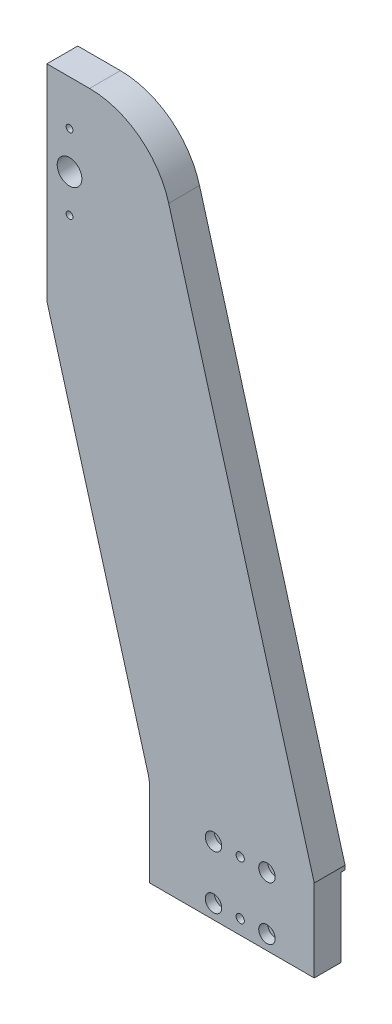
SolidWorks part; units mm, degrees
material "3.3547 (EN-AW 5083)"
ref_plane "Alzado" through (0, 0, 0) normal (0, 0, 1) x (1, 0, 0)
ref_plane "Planta" through (0, 0, 0) normal (0, 1, 0) x (1, 0, 0)
ref_plane "Vista lateral" through (0, 0, 0) normal (1, 0, 0) x (0, 0, -1)
sketch "Croquis1" plane through (0, 0, 0) normal (0, 0, 1) x (1, 0, 0)
  line L0 (80, 0) -> (80, 40)
  line L1 (-50, 320) -> (-29.2688, 320)
  line L2 (-50, 320) -> (-50, 220)
  line L3 (0, 0) -> (80, 0)
  line L4 (9.2285, 290.8607) -> (80, 40)
  line L9 (-50, 220) -> (-0.7513, 45.4303)
  line L11 (0, 40) -> (0, 0)
  arc A2 (9.2285, 290.8607) -> (-29.2688, 320) centre (-29.2688, 280) ccw
  arc A3 (0, 40) -> (-0.7513, 45.4303) centre (-20, 40) ccw
  point P14 (0, 42.7671)
  dimension "D7" = 20
  dimension "D9" = 40
  dimension "D1" = 40
  dimension "D2" = 320
  dimension "D3" = 80
  dimension "D4" = 50
  dimension "D5" = 100
  dimension "D6" = 40
extrude "Saliente-Extruir1" add sketch "Croquis1" along normal blind 15
sketch "Croquis2" plane through (0, 0, 0) normal (0, 0, -1) x (-1, 0, 0)
  line L0 (29.2688, 320) -> (50, 320) construction
  line L2 (50, 320) -> (50, 220) construction
  circle A0 centre (39, 280) radius 6
  dimension "D3" = 12
  dimension "D1" = 40
  dimension "D2" = 11
extrude "Cortar-Extruir1" cut sketch "Croquis2" against normal through all
hole_wizard "Perforador para roscar para macho de roscar para M44" positions "Croquis7" profile "Croquis8" hole size "M4" standard "DIN"
sketch "Croquis7" plane through (0, 0, 15) normal (0, 0, 1) x (1, 0, 0)
  line L0 (-39, 298.25) -> (-39, 261.75)
  circle A0 centre (-39, 280) radius 6 construction
  point P1 (-39, 298.25)
  point P2 (-39, 261.75)
  dimension "D1" = 18.25
  dimension "D2" = 18.25
sketch "Croquis8" plane through (-39, 298.25, 15) normal (1, 0, 0) x (0, -1, 0)
  line L0 (0, 0) -> (0, 7.9914)
  line L1 (0, 7.9914) -> (1.65, 7)
  line L2 (1.65, 7) -> (1.65, 0)
  line L5 (1.65, 0) -> (0, 0)
  line L10 (0, 7.9914) -> (-1.65, 7) construction
  line L11 (0, -6.35) -> (0, 107.95) construction
  dimension "Diámetro de taladro" = 3.3
  dimension "Profundidad de taladro" = 7
  dimension "Ángulo de perforador" = 118
sketch "Croquis9" plane through (0, 0, 0) normal (0, 0, -1) x (-1, 0, 0)
  line L1 (0, 0) -> (-80, 0)
  line L2 (0, 0) -> (0, 38)
  line L3 (0, 38) -> (-80, 38)
  line L4 (-80, 0) -> (-80, 38)
  dimension "D1" = 80
  dimension "D2" = 38
extrude "Cortar-Extruir2" cut sketch "Croquis9" against normal blind 2
hole_wizard "Perforador para roscar para macho de roscar para M45" positions "Croquis10" profile "Croquis11" hole size "M4" standard "DIN"
sketch "Croquis10" plane through (-50, 0, 0) normal (-1, 0, 0) x (0, 0, 1)
  line L0 (15, 320) -> (0, 320) construction
  line L1 (15, 320) -> (15, 220) construction
  point P0 (9, 305)
  point P2 (9, 255)
  dimension "D1" = 15
  dimension "D2" = 65
  dimension "D3" = 6
  dimension "D4" = 6
sketch "Croquis11" plane through (-50, 305, 9) normal (0, 1, 0) x (0, 0, 1)
  line L0 (0, 0) -> (0, 15.9914)
  line L1 (0, 15.9914) -> (1.65, 15)
  line L2 (1.65, 15) -> (1.65, 0)
  line L5 (1.65, 0) -> (0, 0)
  line L10 (0, 15.9914) -> (-1.65, 15) construction
  line L11 (0, -6.35) -> (0, 107.95) construction
  dimension "Diámetro de taladro" = 3.3
  dimension "Profundidad de taladro" = 15
  dimension "Ángulo de perforador" = 118
hole_wizard "Taladros de espiga de Ø4.0mm1" positions "Croquis12" profile "Croquis13" hole size "Ø4.0" standard "DIN"
sketch "Croquis12" plane through (-50, 0, 0) normal (-1, 0, 0) x (0, 0, 1)
  line L0 (15, 320) -> (0, 320) construction
  line L1 (15, 320) -> (15, 220) construction
  point P0 (9, 294)
  point P2 (9, 266)
  dimension "D1" = 26
  dimension "D2" = 54
  dimension "D3" = 6
  dimension "D4" = 6
sketch "Croquis13" plane through (-50, 294, 9) normal (0, 1, 0) x (0, 0, 1)
  line L0 (0, 0) -> (0, 18.2017)
  line L1 (0, 18.2017) -> (2, 17)
  line L2 (2, 17) -> (2, 0)
  line L5 (2, 0) -> (0, 0)
  line L10 (0, 18.2017) -> (-2, 17) construction
  line L11 (0, -6.35) -> (0, 107.95) construction
  dimension "Diámetro de taladro" = 4
  dimension "Profundidad de taladro" = 17
  dimension "Ángulo de perforador" = 118
hole_wizard "Taladros de espiga de Ø4.0mm3" positions "Croquis14" profile "Croquis15" hole size "Ø4.0" standard "DIN" end condition through all
sketch "Croquis14" plane through (0, 0, 15) normal (0, 0, 1) x (1, 0, 0)
  line L0 (44, 33) -> (44, 7) construction
  line L3 (0, 0) -> (80, 0) construction
  line L4 (80, 0) -> (80, 40) construction
  point P1 (44, 33)
  point P2 (44, 7)
  dimension "D1" = 26
  dimension "D2" = 7
  dimension "D3" = 36
sketch "Croquis15" plane through (44, 33, 15) normal (1, 0, 0) x (0, -1, 0)
  line L0 (0, 0) -> (0, 15)
  line L1 (0, 15) -> (2, 15)
  line L2 (2, 15) -> (2, 0)
  line L5 (2, 0) -> (0, 0)
  line L11 (0, -6.35) -> (0, 107.95) construction
  dimension "Diámetro de taladro hasta el siguiente" = 4
  dimension "Profundidad de taladro hasta el siguiente" = 15
hole_wizard "Refrentado para tornillo con cabeza hueca de M41" positions "Croquis16" profile "Croquis17" counterbore size "M4" standard "DIN" end condition through all
sketch "Croquis16" plane through (0, 0, 15) normal (0, 0, 1) x (1, 0, 0)
  line L1 (31, 7) -> (57, 7)
  line L2 (31, 7) -> (31, 33)
  line L3 (31, 33) -> (57, 33)
  line L4 (57, 7) -> (57, 33)
  line L5 (31, 7) -> (57, 33) construction
  line L6 (31, 33) -> (57, 7) construction
  line L7 (0, 0) -> (80, 0) construction
  line L8 (80, 0) -> (80, 40) construction
  point P2 (57, 33)
  point P135 (31, 7)
  point P136 (31, 33)
  point P137 (57, 7)
  dimension "D1" = 26
  dimension "D2" = 26
  dimension "D3" = 7
  dimension "D4" = 23
sketch "Croquis17" plane through (57, 33, 15) normal (1, 0, 0) x (0, -1, 0)
  line L0 (0, 0) -> (0, 15)
  line L1 (0, 15) -> (2.25, 15)
  line L3 (2.25, 15) -> (2.25, 4.4)
  line L4 (2.25, 4.4) -> (4, 4.4)
  line L5 (4, 4.4) -> (4, 0)
  line L7 (4, 0) -> (0, 0)
  line L11 (0, -6.35) -> (0, 107.95) construction
  dimension "Diámetro de taladro hasta el siguiente" = 4.5
  dimension "Profundidad de taladro hasta el siguiente" = 15
  dimension "Diámetro de refrentado" = 8
  dimension "Profundidad de refrentado" = 4.4
